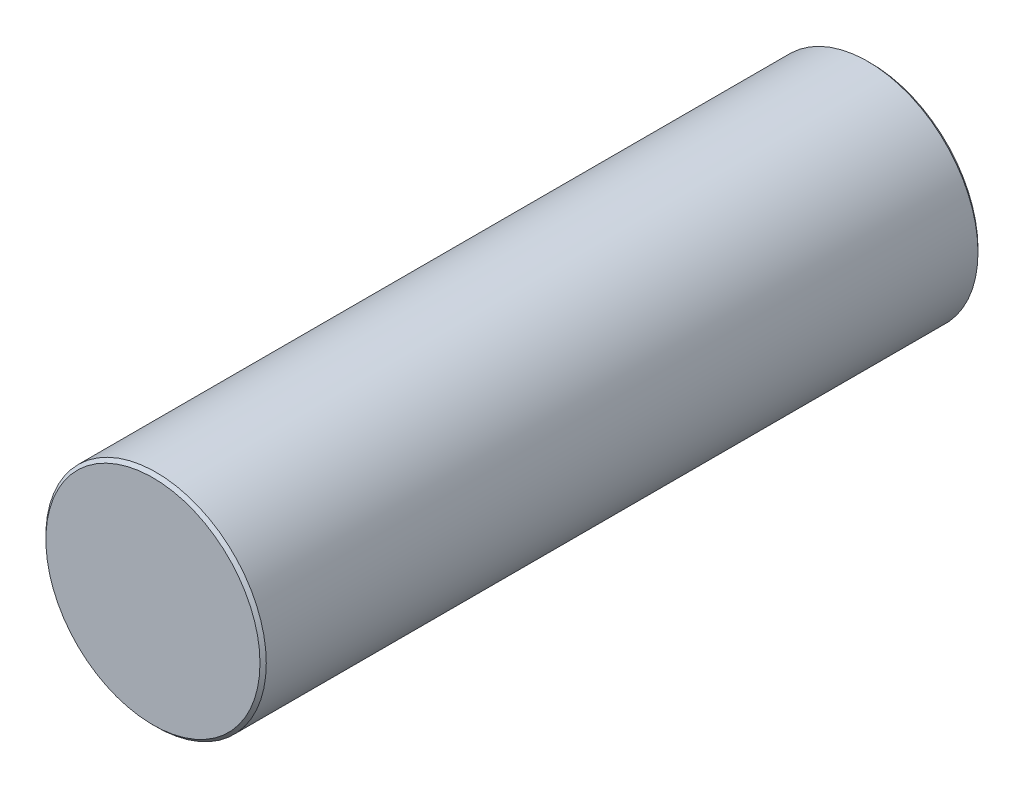
SolidWorks part; units mm, degrees
ref_plane "Front Plane" through (0, 0, 0) normal (0, 0, 1) x (1, 0, 0)
ref_plane "Top Plane" through (0, 0, 0) normal (0, 1, 0) x (1, 0, 0)
ref_plane "Right Plane" through (0, 0, 0) normal (1, 0, 0) x (0, 0, -1)
sketch "Sketch2" plane through (0, 0, 0) normal (0, 0, 1) x (1, 0, 0)
  circle A0 centre (0, 0) radius 1.75
  dimension "D1" = 3.5
extrude "Boss-Extrude1" add sketch "Sketch2" along normal blind 11.4
chamfer "Chamfer2" distance 0.05 angle 45 2 edges at (1.75, 0, 11.4) (1.75, 0, 0)
